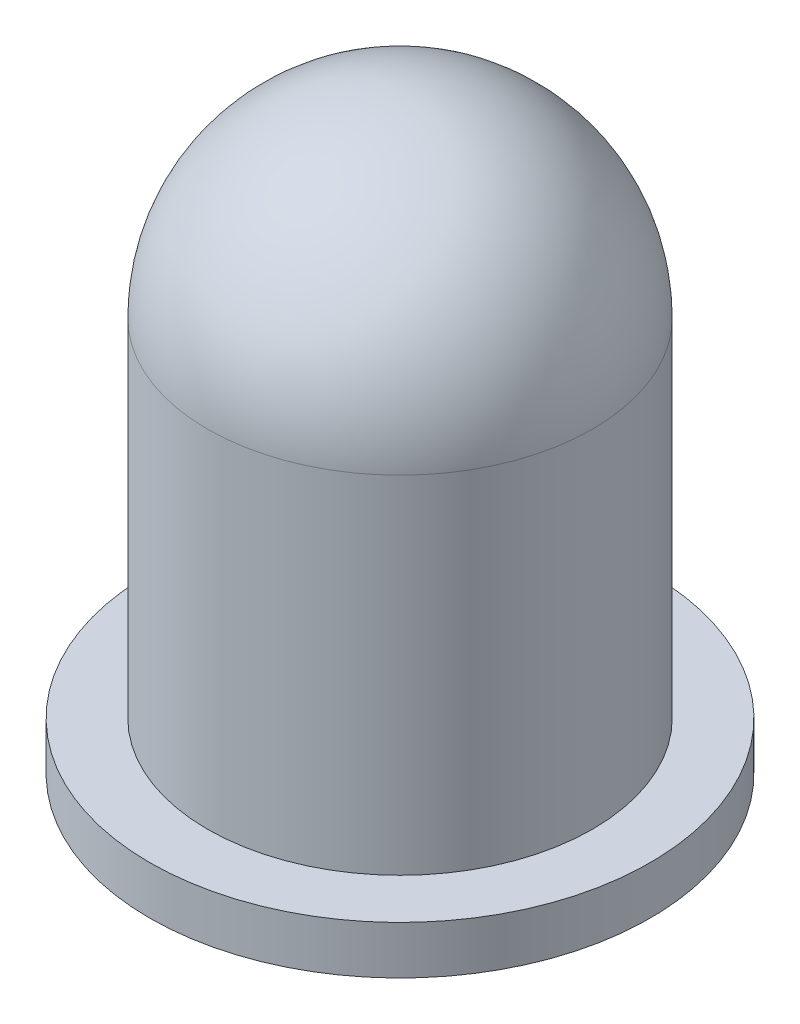
SolidWorks part; units mm, degrees
ref_plane "Front Plane" through (0, 0, 0) normal (0, 0, 1) x (1, 0, 0)
ref_plane "Top Plane" through (0, 0, 0) normal (0, 1, 0) x (1, 0, 0)
ref_plane "Right Plane" through (0, 0, 0) normal (1, 0, 0) x (0, 0, -1)
sketch "Sketch1" plane through (0, 0, 0) normal (0, 0, 1) x (1, 0, 0)
  line L0 (176.9266, 16.8847) -> (176.9266, 20.4847)
  line L2 (176.3266, 16.8847) -> (176.3266, 16.3847)
  line L3 (176.3266, 16.3847) -> (181.5266, 16.3847)
  line L4 (181.5266, 16.8847) -> (181.5266, 16.3847)
  line L5 (181.5266, 16.8847) -> (180.9266, 16.8847)
  line L6 (180.9266, 20.4847) -> (180.9266, 16.8847)
  line L7 (176.9266, 16.8847) -> (176.3266, 16.8847)
  line L8 (178.9266, 29.0978) -> (178.9266, 15.8716)
  arc A0 (176.9266, 20.4847) -> (180.9266, 20.4847) centre (178.9266, 20.4847) cw
  point P12 (178.9266, 22.4847)
  point P13 (178.9266, 22.4847)
  point P16 (178.9266, 20.4847)
  dimension "D1" = 3.6
  dimension "D2" = 0.5
  dimension "D3" = 5.2
  dimension "D4" = 4
  dimension "D5" = 0.6
revolve "Revolve1" add sketch "Sketch1" angle 360 mid plane about L8 region at (177.9339, 19.1706, 0)
